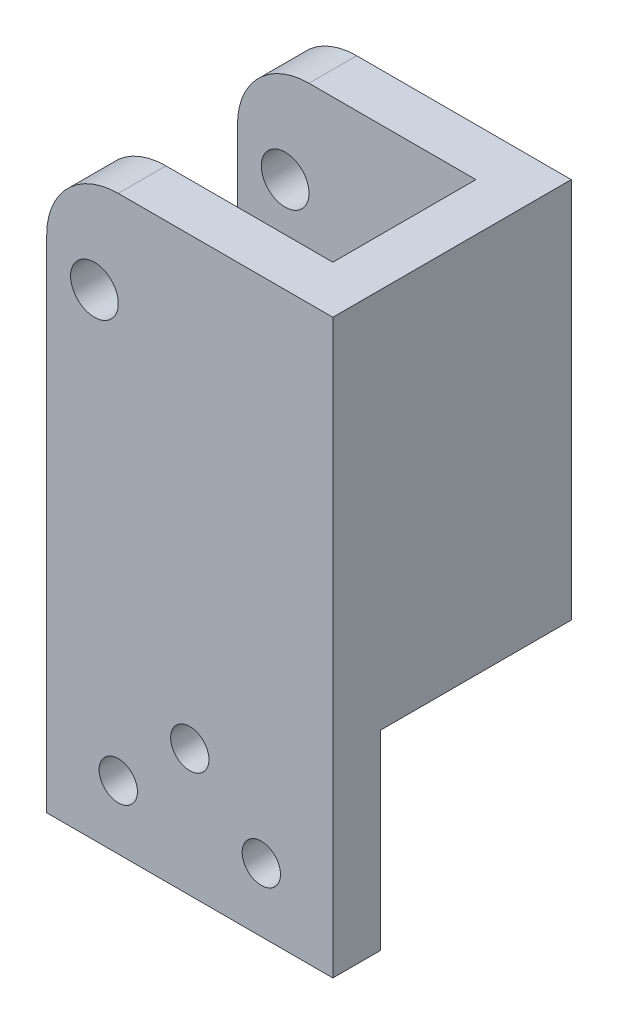
SolidWorks part; units mm, degrees
ref_plane "Front Plane" through (0, 0, 0) normal (0, 0, 1) x (1, 0, 0)
ref_plane "Top Plane" through (0, 0, 0) normal (0, 1, 0) x (1, 0, 0)
ref_plane "Right Plane" through (0, 0, 0) normal (1, 0, 0) x (0, 0, -1)
sketch "Sketch1" plane through (0, 0, 0) normal (0, 0, 1) x (1, 0, 0)
  line L1 (0, 0) -> (38.1, 0)
  line L2 (0, 0) -> (0, 76.2)
  line L3 (0, 76.2) -> (38.1, 76.2)
  line L4 (38.1, 0) -> (38.1, 76.2)
  dimension "D1" = 76.2
  dimension "D2" = 38.1
extrude "Boss-Extrude1" add sketch "Sketch1" against normal blind 31.75
sketch "Sketch2" plane through (0, 76.2, 0) normal (0, 1, 0) x (1, 0, 0)
  line L0 (0, 0) -> (0, 6.35)
  line L1 (0, 31.75) -> (0, 0) construction
  line L2 (0, 6.35) -> (31.75, 6.35)
  line L3 (31.75, 6.35) -> (31.75, 31.75)
  line L4 (38.1, 31.75) -> (0, 31.75) construction
  line L5 (38.1, 31.75) -> (38.1, 0) construction
  line L6 (31.75, 6.35) -> (31.75, 25.4) construction
  dimension "D1" = 6.35
  dimension "D2" = 6.35
  dimension "D3" = 19.05
sketch "Sketch3" plane through (0, 0, 0) normal (-1, 0, 0) x (0, 0, 1)
  line L0 (-31.75, 0) -> (-6.35, 0)
  line L1 (-31.75, 0) -> (0, 0) construction
  line L4 (-31.75, 0) -> (-31.75, 76.2)
  line L5 (-31.75, 76.2) -> (-6.35, 76.2)
  line L6 (-6.35, 0) -> (-6.35, 76.2)
  dimension "D1" = 25.4
  dimension "D2" = 76.2
extrude "Cut-Extrude2" cut sketch "Sketch3" against normal blind 31.75
sketch "Sketch4" plane through (31.75, 0, 0) normal (-1, 0, 0) x (0, 0, 1)
  line L0 (-6.35, 0) -> (-6.35, 76.2) construction
  line L1 (-31.75, 0) -> (-6.35, 0)
  line L2 (-31.75, 0) -> (-31.75, 25.4)
  line L3 (-31.75, 25.4) -> (-6.35, 25.4)
  line L4 (-6.35, 0) -> (-6.35, 25.4)
  dimension "D1" = 25.4
extrude "Cut-Extrude3" cut sketch "Sketch4" against normal through all
sketch "Sketch5" plane through (0, 76.2, 0) normal (0, 1, 0) x (1, 0, 0)
  line L0 (38.1, 31.75) -> (38.1, 0) construction
  line L1 (38.1, 0) -> (0, 0) construction
  line L2 (0, 0) -> (0, 6.35) construction
  line L3 (0, 6.35) -> (31.75, 6.35) construction
  line L4 (31.75, 6.35) -> (31.75, 31.75) construction
  line L5 (31.75, 31.75) -> (38.1, 31.75) construction
  line L6 (31.75, 6.35) -> (31.75, 25.4)
  line L7 (31.75, 31.75) -> (0, 31.75)
  line L8 (0, 31.75) -> (0, 25.4)
  line L9 (0, 25.4) -> (31.75, 25.4)
  line M6 (31.75, 31.75) -> (31.75, 6.35)
  dimension "D1" = 19.05
extrude "Boss-Extrude2" add sketch "Sketch5" against normal blind 50.8 contours L8 L9 L7 M6 region at (15.875, 76.2, -28.575)
sketch "Sketch6" plane through (0, 0, -31.75) normal (0, 0, -1) x (-1, 0, 0)
  line L0 (0, 76.2) -> (0, 63.5) construction
  line L1 (0, 25.4) -> (0, 76.2) construction
  line L2 (0, 63.5) -> (-6.35, 63.5) construction
  circle A0 centre (-6.35, 63.5) radius 3.175
  dimension "D3" = 6.35
  dimension "D1" = 12.7
  dimension "D2" = 6.35
extrude "Cut-Extrude4" cut sketch "Sketch6" against normal blind 50.8
fillet "Fillet2" radius 9.525 2 edges at (0, 76.2, -3.175) (0, 76.2, -28.575)
ref_plane "Plane1" through (0, 25.4, 0) normal (0, -1, 0) x (-1, 0, 0)
sketch "Sketch7" plane through (0, 25.4, 0) normal (0, -1, 0) x (-1, 0, 0)
  line L1 (0, 25.4) -> (-31.75, 25.4)
  line L2 (0, 25.4) -> (0, 6.35)
  line L3 (0, 6.35) -> (-31.75, 6.35)
  line L4 (-31.75, 25.4) -> (-31.75, 6.35)
extrude "Boss-Extrude3" add sketch "Sketch7" against normal blind 6.35
sketch "Sketch8" plane through (0, 0, 0) normal (0, 0, 1) x (1, 0, 0)
  line L0 (38.1, 0) -> (38.1, 76.2) construction
  line L1 (0, 0) -> (38.1, 0)
  line L2 (0, 0) -> (0, 25.4)
  line L3 (0, 25.4) -> (38.1, 25.4)
  line L4 (38.1, 0) -> (38.1, 25.4)
  line L5 (9.525, 0) -> (9.525, 25.4) construction
  line L6 (19.05, 0) -> (19.05, 25.4) construction
  line L7 (28.575, 0) -> (28.575, 25.4) construction
  line L8 (0, 8.4667) -> (38.1, 8.4667) construction
  line L9 (0, 16.9333) -> (38.1, 16.9333) construction
  point P20 (19.05, 16.9333)
  point P21 (9.525, 8.4667)
  point P22 (28.575, 8.4667)
  dimension "D4" = 8.4667
  dimension "D5" = 8.4667
  dimension "D1" = 25.4
  dimension "D2" = 9.525
  dimension "D3" = 9.525
hole_wizard "1/4-20 Tapped Hole2" positions "3DSketch2" profile "Sketch10" tap size "1/4-20" standard "ANSI Inch"
sketch3d "3DSketch2"
  point P0 (9.525, 8.4667, 0)
  point P3 (19.05, 16.9333, 0)
  point P6 (28.575, 8.4667, 0)
sketch "Sketch10" plane through (9.525, 8.4667, 0) normal (1, 0, 0) x (0, -1, 0)
  line L0 (0, 0) -> (0, 18.0438)
  line L1 (0, 18.0438) -> (2.5527, 16.51)
  line L2 (2.5527, 16.51) -> (2.5527, 0)
  line L5 (2.5527, 0) -> (0, 0)
  line L10 (0, 18.0438) -> (-2.5527, 16.51) construction
  line L11 (0, -6.35) -> (0, 107.95) construction
  dimension "Tap Drill Dia." = 5.1054
  dimension "Tap Drill Depth" = 16.51
  dimension "Drill Angle" = 118
